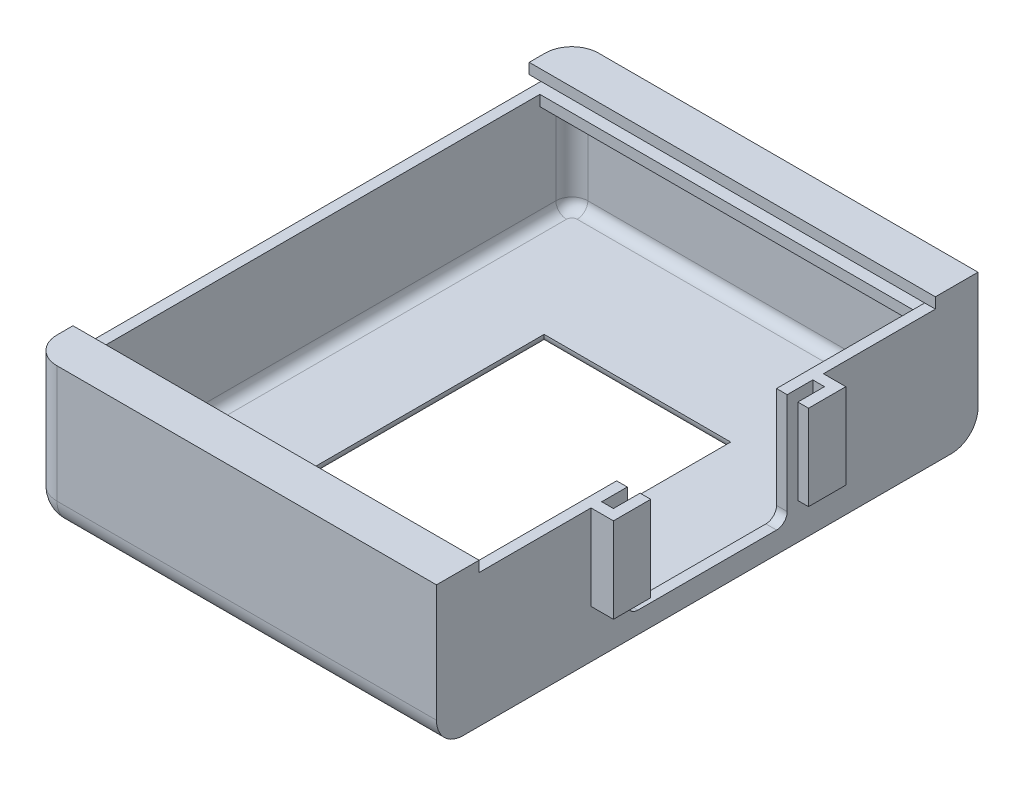
SolidWorks part; units mm, degrees
ref_plane "Front Plane" through (0, 0, 0) normal (0, 0, 1) x (1, 0, 0)
ref_plane "Top Plane" through (0, 0, 0) normal (0, 1, 0) x (1, 0, 0)
ref_plane "Right Plane" through (0, 0, 0) normal (1, 0, 0) x (0, 0, -1)
sketch "Sketch1" plane through (0, 0, 0) normal (0, 1, 0) x (1, 0, 0)
  line L1 (38.1, -50.8) -> (-38.1, -50.8)
  line L2 (38.1, -50.8) -> (38.1, 50.8)
  line L3 (38.1, 50.8) -> (-38.1, 50.8)
  line L4 (-38.1, -50.8) -> (-38.1, 50.8)
  line L5 (38.1, -50.8) -> (-38.1, 50.8) construction
  line L6 (38.1, 50.8) -> (-38.1, -50.8) construction
  point P0 (0, 0)
  dimension "D1" = 101.6
  dimension "6in" = 76.2
extrude "Boss-Extrude1" add sketch "Sketch1" along normal blind 25
shell "Shell1" thickness 2 removed face at (0, 25, 0)
sketch "Sketch2" plane through (0, 2, 0) normal (0, 1, 0) x (1, 0, 0)
  line L1 (17.5, -25) -> (-17.5, -25)
  line L2 (17.5, -25) -> (17.5, 25)
  line L3 (17.5, 25) -> (-17.5, 25)
  line L4 (-17.5, -25) -> (-17.5, 25)
  line L5 (17.5, -25) -> (-17.5, 25) construction
  line L6 (17.5, 25) -> (-17.5, -25) construction
  point P0 (0, 0)
  point P5 (0, 0)
  dimension "D1" = 35
  dimension "D2" = 50
extrude "Cut-Extrude1" cut sketch "Sketch2" against normal blind 25
sketch "Sketch3" plane through (38.1, 0, 0) normal (1, 0, 0) x (0, 0, -1)
  line L0 (-50.8, 25) -> (50.8, 25) construction
  line L1 (-15, 46) -> (15, 46)
  line L2 (-15, 46) -> (-15, 6)
  line L3 (-13, 4) -> (13, 4)
  line L4 (15, 46) -> (15, 6)
  line L5 (-15, 46) -> (15, 4) construction
  line L6 (-15, 4) -> (15, 46) construction
  line L7 (-50.8, 0) -> (50.8, 0) construction
  arc A0 (-15, 6) -> (-13, 4) centre (-13, 6) ccw
  arc A1 (13, 4) -> (15, 6) centre (13, 6) ccw
  point P0 (0, 25)
  dimension "D3" = 2
  dimension "D1" = 30
  dimension "D2" = 4
extrude "Cut-Extrude2" cut sketch "Sketch3" against normal up to next
fillet "Fillet1" radius 5 2 edges at (-38.1, 12.5, 50.8) (-38.1, 12.5, -50.8)
fillet "Fillet2" radius 3 4 edges at (36.1, 13.5, -48.8) (36.1, 13.5, 48.8) (-36.1, 13.5, 48.8) (-36.1, 13.5, -48.8)
fillet "Fillet3" radius 2 8 edges at (35.2213, 2, 47.9213) (0, 2, 48.8) (-35.2213, 2, 47.9213) (-36.1, 2, 0) (-35.2213, 2, -47.9213) (0, 2, -48.8) (35.2213, 2, -47.9213) (36.1, 2, 0)
fillet "Fillet4" radius 5 5 edges at (2.5, 0, 50.8) (-36.6355, 0, 49.3355) (-38.1, 0, 0) (-36.6355, 0, -49.3355) (2.5, 0, -50.8)
sketch "Sketch7" plane through (0, 25, 0) normal (0, 1, 0) x (1, 0, 0)
  line L0 (-36.1, -45.8) -> (36.1, -45.8)
  line L1 (33.1, -48.8) -> (-33.1, -48.8) construction
  line L2 (33.1, -48.8) -> (-33.1, -48.8)
  line L3 (-33.1, 48.8) -> (33.1, 48.8) construction
  line L4 (-33.1, 48.8) -> (33.1, 48.8)
  line L5 (-36.1, 45.8) -> (36.1, 45.8)
  arc A0 (-36.1, -45.8) -> (-33.1, -48.8) centre (-33.1, -45.8) ccw construction
  arc A1 (33.1, -48.8) -> (36.1, -45.8) centre (33.1, -45.8) ccw construction
  arc A2 (-36.1, -45.8) -> (-33.1, -48.8) centre (-33.1, -45.8) ccw
  arc A3 (33.1, -48.8) -> (36.1, -45.8) centre (33.1, -45.8) ccw
  arc A4 (-33.1, 48.8) -> (-36.1, 45.8) centre (-33.1, 45.8) ccw construction
  arc A5 (36.1, 45.8) -> (33.1, 48.8) centre (33.1, 45.8) ccw construction
  arc A6 (-33.1, 48.8) -> (-36.1, 45.8) centre (-33.1, 45.8) ccw
  arc A7 (36.1, 45.8) -> (33.1, 48.8) centre (33.1, 45.8) ccw
extrude "Boss-Extrude4" add sketch "Sketch7" against normal blind 2.2 separate body
sketch "Sketch4" plane through (-38.1, 0, 0) normal (-1, 0, 0) x (0, 0, 1)
  line L0 (-45.8, 25) -> (45.8, 25) construction
  line L1 (45.8, 27.2) -> (-45.8, 27.2)
  line L2 (45.8, 27.2) -> (45.8, 22.8)
  line L3 (45.8, 22.8) -> (-45.8, 22.8)
  line L4 (-45.8, 27.2) -> (-45.8, 22.8)
  line L5 (45.8, 27.2) -> (-45.8, 22.8) construction
  line L6 (45.8, 22.8) -> (-45.8, 27.2) construction
  line L7 (-45.8, 25) -> (-45.8, 5) construction
  point P0 (0, 25)
  dimension "D1" = 2.2
extrude "Cut-Extrude3" cut sketch "Sketch4" against normal up to next (2 mm away)
sketch "Sketch5" plane through (0, 25, 0) normal (0, 1, 0) x (1, 0, 0)
  line L0 (-33.1, -50.8) -> (38.1, -50.8) construction
  line L1 (38.1, 50.8) -> (-33.1, 50.8) construction
  line L2 (-33.1, -50.8) -> (38.1, -50.8)
  line L3 (38.1, 50.8) -> (-33.1, 50.8)
  line L4 (-38.1, -45.8) -> (-38.1, -42.8)
  line L5 (-38.1, 45.8) -> (-38.1, -45.8) construction
  line L6 (-38.1, -42.8) -> (38.1, -42.8)
  line L7 (38.1, -50.8) -> (38.1, -15) construction
  line L8 (38.1, -42.8) -> (38.1, -50.8)
  line L9 (-38.1, 45.8) -> (-38.1, 42.8)
  line L10 (-38.1, 42.8) -> (38.1, 42.8)
  line L11 (38.1, 15) -> (38.1, 50.8) construction
  line L12 (38.1, 42.8) -> (38.1, 50.8)
  arc A0 (-38.1, -45.8) -> (-33.1, -50.8) centre (-33.1, -45.8) ccw construction
  arc A1 (-33.1, 50.8) -> (-38.1, 45.8) centre (-33.1, 45.8) ccw construction
  arc A2 (-38.1, -45.8) -> (-33.1, -50.8) centre (-33.1, -45.8) ccw
  arc A3 (-33.1, 50.8) -> (-38.1, 45.8) centre (-33.1, 45.8) ccw
  dimension "D1" = 8
extrude "Boss-Extrude2" add sketch "Sketch5" along normal blind 2
pattern_linear "LPattern1" count 2 spacing 4.2 along (0, -1, 0) of "Boss-Extrude2"
sketch "Sketch6" plane through (0, 0, 0) normal (0, -1, 0) x (1, 0, 0)
  line L1 (38.1, 45.8) -> (38.1, -45.8) construction
  line L8 (38.1, -19.8) -> (38.1, -21.8)
  line L10 (0, 0) -> (38.1, 0) construction
  line L19 (38.1, -21.8) -> (42.3, -21.8)
  line L20 (42.3, -21.8) -> (42.3, -14.8)
  line L21 (42.3, -14.8) -> (40.3, -14.8)
  line L22 (40.3, -14.8) -> (40.3, -19.8)
  line L23 (40.3, -19.8) -> (38.1, -19.8)
  line L24 (38.1, -50.8) -> (-33.1, -50.8) construction
  line L25 (40.3, 19.8) -> (38.1, 19.8)
  line L26 (40.3, 14.8) -> (40.3, 19.8)
  line L27 (42.3, 14.8) -> (40.3, 14.8)
  line L28 (42.3, 21.8) -> (42.3, 14.8)
  line L29 (38.1, 21.8) -> (42.3, 21.8)
  line L30 (38.1, 19.8) -> (38.1, 21.8)
  point P4 (38.1, -20.8)
  dimension "D1" = 2
  dimension "D2" = 2
  dimension "D3" = 30
  dimension "D4" = 2.2
  dimension "D5" = 5
extrude "Boss-Extrude3" add sketch "Sketch6" against normal up to surface (25 mm away) from offset 9 up to face at (37.1, 25, -28.9) offset against normal yes
sketch "Sketch8" plane through (-38.1, 0, 0) normal (-1, 0, 0) x (0, 0, 1)
  line L1 (9.7, 6.3224) -> (-9.7, 6.3224)
  line L2 (12.7, 9.3224) -> (12.7, 18.3224)
  line L3 (9.7, 21.3224) -> (-9.7, 21.3224)
  line L4 (-12.7, 9.3224) -> (-12.7, 18.3224)
  line L5 (12.7, 6.3224) -> (-12.7, 21.3224) construction
  line L6 (12.7, 21.3224) -> (-12.7, 6.3224) construction
  arc A0 (9.7, 6.3224) -> (12.7, 9.3224) centre (9.7, 9.3224) ccw
  arc A1 (12.7, 18.3224) -> (9.7, 21.3224) centre (9.7, 18.3224) ccw
  arc A2 (-9.7, 21.3224) -> (-12.7, 18.3224) centre (-9.7, 18.3224) ccw
  arc A3 (-9.7, 6.3224) -> (-12.7, 9.3224) centre (-9.7, 9.3224) cw
  point P0 (0, 13.8224)
  point P5 (0, 13.8224)
  dimension "D3" = 3
  dimension "D1" = 25.4
  dimension "D2" = 15
fillet "Fillet5" radius 2 4 edges at (17.5, 0, 0) (0, 0, 25) (-17.5, 0, 0) (0, 0, -25)
